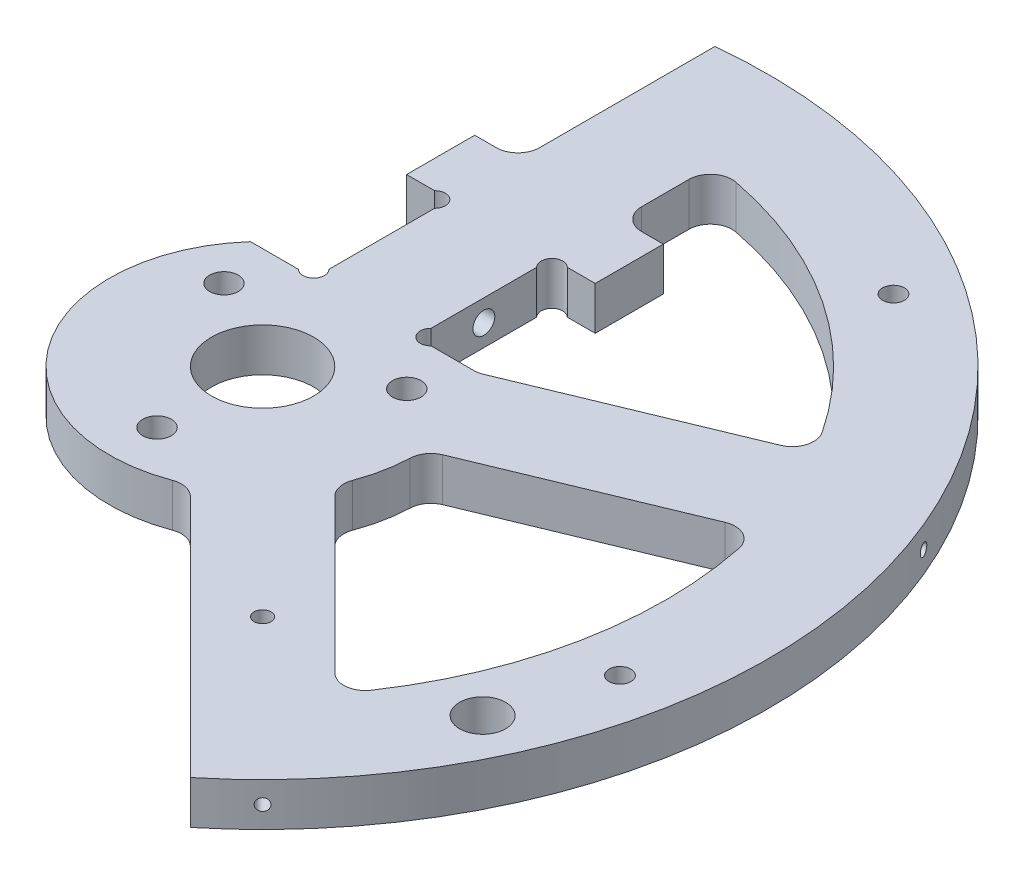
SolidWorks part; units mm, degrees
material "6061 Alloy"
ref_plane "Front Plane" through (0, 0, 0) normal (0, 0, 1) x (1, 0, 0)
ref_plane "Top Plane" through (0, 0, 0) normal (0, 1, 0) x (1, 0, 0)
ref_plane "Right Plane" through (0, 0, 0) normal (1, 0, 0) x (0, 0, -1)
sketch "Sketch1" plane through (0, 0, 0) normal (0, 1, 0) x (1, 0, 0)
  line L0 (0, 0) -> (0, 74.3) construction
  line L1 (0, 0) -> (52.538, -52.538) construction
  line L2 (20.3033, -9.6967) -> (46.898, -36.2914)
  line L3 (7.5, 15) -> (7.5, 35)
  line L4 (-7.5, -3.1066) -> (-5.3033, -5.3033) construction
  line L5 (-7.5, 21.2132) -> (-7.5, 14.1697) construction
  line L6 (-7.5, -3.1066) -> (-7.5, 74.3) construction
  line L7 (7.5, 3.1066) -> (7.5, 74.3) construction
  line L8 (-7.5, -3.1066) -> (47.2347, -57.8413) construction
  line L9 (7.5, 3.1066) -> (57.8413, -47.2347) construction
  line L10 (46.898, -36.2914) -> (57.573, -46.9664) construction
  line L11 (7.5, 58.8238) -> (7.5, 73.9205) construction
  line L12 (0, 0) -> (68.6442, 28.4334) construction
  line L13 (22.4686, 1.1888) -> (57.2162, 15.5818)
  line L14 (-2.8701, 6.9291) -> (0, 8.1179) construction
  line L15 (2.8701, -6.9291) -> (5.7403, -5.7403) construction
  line L16 (2.8701, -6.9291) -> (71.5144, 21.5043) construction
  line L17 (5.7403, -5.7403) -> (13.2403, -2.6336) construction
  line L18 (7.5, 3.1066) -> (13.2403, -2.6336) construction
  line L19 (7.5, 3.1066) -> (7.5, 11.2245) construction
  line L20 (0, 8.1179) -> (7.5, 11.2245) construction
  line L21 (7.5, 11.2245) -> (9.0849, 11.881) construction
  line L22 (-2.8701, 6.9291) -> (65.7741, 35.3625) construction
  line L23 (51.476, 29.44) -> (65.4235, 35.2172) construction
  line L24 (65.4235, 35.2172) -> (65.7741, 35.3625)
  line L25 (57.2162, 15.5818) -> (71.1638, 21.3591) construction
  line L26 (71.1638, 21.3591) -> (71.5144, 21.5043)
  line L27 (13.2403, -2.6336) -> (20.3033, -9.6967) construction
  line L28 (13.85, 5) -> (7.5, 5) construction
  line L29 (13.85, 17.7321) -> (13.85, 15) construction
  line L30 (13.85, 45) -> (7.5, 45)
  line L31 (-13.85, 17.7321) -> (-13.85, 15) construction
  line L32 (13.85, 5) -> (-13.85, 45) construction
  line L33 (13.85, 45) -> (-13.85, 5) construction
  line L34 (-13.85, 35) -> (-7.5, 35)
  line L35 (-13.85, 35) -> (-13.85, 15) construction
  line L36 (-16.7705, 15) -> (-7.5, 15)
  line L37 (-7.5, 35) -> (-7.5, 15)
  line L38 (7.5, 15) -> (16.6148, 15)
  line L39 (7.5, 15) -> (7.5, 35)
  line L40 (7.5, 35) -> (13.85, 35)
  line L41 (13.85, 15) -> (13.85, 35) construction
  line L42 (13.2403, -2.6336) -> (22.4686, 1.1888) construction
  line L43 (7.5, 5) -> (-7.5274, 5) construction
  line L44 (-7.5, 5) -> (-13.85, 5) construction
  line L45 (-7.5274, 5) -> (0, 5) construction
  line L46 (0, 5) -> (-7.5, 5) construction
  line L47 (13.85, 5) -> (13.85, 13.8548) construction
  line L48 (16.6148, 15) -> (16.7283, 15.047)
  line L49 (16.7283, 15.047) -> (51.476, 29.44)
  line L50 (13.85, 13.8548) -> (13.85, 17.7321) construction
  line L51 (9.0849, 11.881) -> (13.85, 13.8548) construction
  line L52 (7.5, 11.2245) -> (7.5, 21.2132) construction
  line L53 (7.5, 21.2132) -> (7.5, 14.1697) construction
  line L54 (-5.3033, -5.3033) -> (9.6967, -20.3033) construction
  line L55 (9.6967, -20.3033) -> (46.9664, -57.573)
  line L56 (-7.5, -3.1066) -> (-7.5, 0) construction
  line L57 (-7.5, 0) -> (-7.5, 5) construction
  line L58 (-13.85, 5) -> (-13.85, 17.7321) construction
  line L59 (-7.5, 5) -> (-7.5, 21.2132) construction
  line L60 (-7.5, 14.1697) -> (-7.5, 15) construction
  line L61 (-7.5, 15) -> (-7.5, 35) construction
  line L62 (-13.85, 15) -> (-13.85, 35) construction
  line L63 (-13.85, 35) -> (-13.85, 45)
  line L64 (13.85, 15) -> (13.85, 35) construction
  line L65 (13.85, 35) -> (13.85, 45)
  line L66 (0, 45) -> (-7.5, 45) construction
  line L67 (-7.5, 45) -> (-13.85, 45)
  line L68 (7.5, 45) -> (0, 45) construction
  line L69 (7.5, 14.1697) -> (7.5, 15) construction
  line L70 (7.5, 35.8303) -> (7.5, 45) construction
  line L71 (7.5, 45) -> (7.5, 58.8238)
  line L72 (7.5, 35) -> (7.5, 35.8303) construction
  line L73 (-7.5, 35) -> (-7.5, 35.8303) construction
  line L74 (-7.5, 45) -> (-7.5, 73.9205)
  line L75 (-7.5, 35.8303) -> (-7.5, 45) construction
  line L77 (13.85, 13.8548) -> (16.6148, 15) construction
  arc A0 (46.9664, -57.573) -> (-7.5, 73.9205) centre (0, 0) ccw
  arc A1 (46.898, -36.2914) -> (57.2162, 15.5818) centre (0, 0) ccw
  arc A2 (-7.5, 73.9205) -> (46.9664, -57.573) centre (0, 0) ccw construction
  circle A3 centre (0, 0) radius 74.3 construction
  arc A4 (41.9314, -41.9314) -> (46.898, -36.2914) centre (0, 0) ccw construction
  circle A5 centre (0, 0) radius 59.3 construction
  arc A6 (36.2914, -46.898) -> (41.9314, -41.9314) centre (0, 0) ccw construction
  arc A7 (-7.5, 58.8238) -> (36.2914, -46.898) centre (0, 0) ccw construction
  arc A8 (7.5, 58.8238) -> (0, 59.3) centre (0, 0) ccw construction
  arc A9 (0, 59.3) -> (-7.5, 58.8238) centre (0, 0) ccw construction
  arc A10 (57.2162, 15.5818) -> (54.7861, 22.6931) centre (0, 0) ccw construction
  arc A11 (51.476, 29.44) -> (7.5, 58.8238) centre (0, 0) ccw
  arc A12 (54.7861, 22.6931) -> (51.476, 29.44) centre (0, 0) ccw construction
  arc A13 (20.3033, -9.6967) -> (22.4686, 1.1888) centre (0, 0) ccw
  circle A14 centre (0, 0) radius 7.5
  arc A15 (9.6967, -20.3033) -> (15.9099, -15.9099) centre (0, 0) ccw construction
  arc A16 (15.9099, -15.9099) -> (20.3033, -9.6967) centre (0, 0) ccw construction
  arc A17 (22.4686, 1.1888) -> (20.7873, 8.6104) centre (0, 0) ccw construction
  arc A18 (16.7283, 15.047) -> (13.85, 17.7321) centre (0, 0) ccw construction
  arc A19 (20.7873, 8.6104) -> (16.7283, 15.047) centre (0, 0) ccw construction
  arc A20 (13.85, 17.7321) -> (1.7801, 22.4295) centre (0, 0) ccw construction
  arc A21 (-7.5, 21.2132) -> (-13.85, 17.7321) centre (0, 0) ccw construction
  arc A22 (1.7801, 22.4295) -> (-13.85, 17.7321) centre (0, 0) ccw construction
  arc A23 (7.5, 21.2132) -> (0, 22.5) centre (0, 0) ccw construction
  arc A24 (0, 22.5) -> (-7.5, 21.2132) centre (0, 0) ccw construction
  arc A25 (-1.7801, 22.4295) -> (-13.85, 17.7321) centre (0, 0) ccw construction
  arc A26 (-16.7705, 15) -> (9.6967, -20.3033) centre (0, 0) ccw
  arc A27 (-13.85, 17.7321) -> (-16.7705, 15) centre (0, 0) ccw construction
  arc A28 (-16.7705, 15) -> (-1.7801, 22.4295) centre (0, 0) ccw construction
  arc A29 (-13.85, 17.7321) -> (-16.7705, 15) centre (0, 0) ccw construction
  arc A30 (-13.85, 17.7321) -> (-16.7705, 15) centre (0, 0) ccw construction
  arc A31 (-16.7705, 15) -> (7.5, 21.2132) centre (0, 0) ccw construction
  point P77 (0, 25)
  dimension "D1" = 148.6
  dimension "D11" = 45
  dimension "D12" = 15
  dimension "D2" = 135
  dimension "D6" = 67.5
  dimension "D9" = 27.7
  dimension "D10" = 40
  dimension "D13" = 5
  dimension "D14" = 10
  dimension "D15" = 10
  dimension "D3" = 7.5
  dimension "D4" = 7.5
  dimension "D5" = 15
  dimension "D7" = 7.5
  dimension "D8" = 7.5
extrude "Boss-Extrude1" add sketch "Sketch1" along normal mid plane 6.35 contours L31 A26 L55 A0 L74 L67 L63 L34 L37 L36 L49 A18 L29 L38 L3 L40 L65 L30 L71 A11 L2 A13 L13 A1 A14 region at (27.267, 0, -11.9761)
hole_wizard "M5x0.8 Tapped Hole2" positions "Sketch2" profile "Sketch3" tap size "M5x0.8" standard "ANSI Metric" end condition through all
sketch "Sketch2" plane through (0, 3.175, 0) normal (0, 1, 0) x (1, 0, 0)
  line L1 (0, 0) -> (-13.4234, 7.75) construction
  line L3 (13.4234, 7.75) -> (0, 0) construction
  line L4 (0, 0) -> (0, -15.5) construction
  circle A0 centre (0, 0) radius 15.5 construction
  point P10 (-13.4234, 7.75)
  point P12 (13.4234, 7.75)
  point P16 (0, -15.5)
  dimension "D1" = 31
  dimension "D2" = 120
  dimension "D3" = 120
sketch "Sketch3" plane through (0, 3.175, 15.5) normal (1, 0, 0) x (0, 0, 1)
  line L0 (0, 0) -> (0, 6.35)
  line L1 (0, 6.35) -> (2.1, 6.35)
  line L2 (2.1, 6.35) -> (2.1, 0)
  line L5 (2.1, 0) -> (0, 0)
  line L11 (0, -6.35) -> (0, 107.95) construction
  dimension "Thru Tap Drill Dia." = 4.2
  dimension "Thru Tap Drill Depth" = 6.35
ref_plane "Plane1" through (0, 0, -74.3) normal (0, 0, -1) x (-1, 0, 0)
hole_wizard "M2.2x0.45 Tapped Hole1" positions "Sketch4" profile "Sketch5" tap size "M2.2x0.45" standard "ANSI Metric"
sketch "Sketch4" plane through (0, 0, -74.3) normal (0, 0, -1) x (-1, 0, 0)
  point P0 (0, 0)
sketch "Sketch5" plane through (0, 0, -74.3) normal (1, 0, 0) x (0, 1, 0)
  line L0 (0, 0) -> (0, 10.5258)
  line L1 (0, 10.5258) -> (0.875, 10)
  line L2 (0.875, 10) -> (0.875, 0)
  line L5 (0.875, 0) -> (0, 0)
  line L10 (0, 10.5258) -> (-0.875, 10) construction
  line L11 (0, -6.35) -> (0, 107.95) construction
  dimension "Tap Drill Dia." = 1.75
  dimension "Tap Drill Depth" = 10
  dimension "Drill Angle" = 118
pattern_circular "CirPattern1" count 3 over 135 about axis through (0, 3.175, 0) along (0, -1, 0) of "M2.2x0.45 Tapped Hole1"
hole_wizard "M3 Clearance Hole1" positions "Sketch6" profile "Sketch7" hole size "M3" standard "ANSI Metric" end condition up to next
sketch "Sketch6" plane through (-7.5, 0, 0) normal (-1, 0, 0) x (0, 0, 1)
  line L1 (-35, 3.175) -> (-15, 3.175)
  line L2 (-35, 3.175) -> (-35, -3.175)
  line L3 (-35, -3.175) -> (-15, -3.175)
  line L4 (-15, 3.175) -> (-15, -3.175)
  line L5 (-35, 3.175) -> (-15, -3.175) construction
  line L6 (-35, -3.175) -> (-15, 3.175) construction
  point P199 (-25, 0)
sketch "Sketch7" plane through (-7.5, 0, -25) normal (0, 1, 0) x (0, 0, 1)
  line L0 (0, 0) -> (0, 15)
  line L1 (0, 15) -> (1.6, 15)
  line L2 (1.6, 15) -> (1.6, 0)
  line L5 (1.6, 0) -> (0, 0)
  line L11 (0, -6.35) -> (0, 107.95) construction
  dimension "Thru Hole Dia." = 3.2
  dimension "Thru Hole Depth" = 15
hole_wizard "CSK for M3 Flat Head Machine Screw1" positions "Sketch8" profile "Sketch9" countersink size "M3" standard "ANSI Metric" end condition up to next
sketch "Sketch8" plane through (0, -3.175, 0) normal (0, -1, 0) x (-1, 0, 0)
  line L0 (-58.1606, -11.5689) -> (-72.8723, -14.4952) construction
  line L2 (-32.9453, 49.3061) -> (-41.2789, 61.7782) construction
  arc A0 (-57.2162, 15.5818) -> (-46.898, -36.2914) centre (0, 0) ccw construction
  arc A1 (7.5, 73.9205) -> (-46.9664, -57.573) centre (0, 0) ccw construction
  arc A2 (-7.5, 58.8238) -> (-51.476, 29.44) centre (0, 0) ccw construction
  point P19 (-65.5165, -13.032)
  point P21 (-37.1121, 55.5422)
sketch "Sketch9" plane through (37.1121, -3.175, -55.5422) normal (1, 0, 0) x (0, 0, -1)
  line L0 (0, 0) -> (0, 6.35)
  line L1 (0, 6.35) -> (1.6, 6.35)
  line L2 (1.6, 6.35) -> (1.6, 1.55)
  line L3 (1.6, 1.55) -> (3.15, 0)
  line L5 (3.15, 0) -> (0, 0)
  line L6 (-1.6, 1.55) -> (-3.15, 0) construction
  line L11 (0, -6.35) -> (0, 107.95) construction
  dimension "Thru Hole Dia." = 3.2
  dimension "Thru Hole Depth" = 6.35
  dimension "Near C'Sink Dia." = 6.3
  dimension "Near C'Sink Angle" = 90
hole_wizard "M3x0.5 Tapped Hole1" positions "Sketch10" profile "Sketch11" tap size "M3x0.5" standard "ANSI Metric" end condition up to next
sketch "Sketch10" plane through (0, -3.175, 0) normal (0, -1, 0) x (-1, 0, 0)
  line L5 (-9.6967, -20.3033) -> (-46.9664, -57.573) construction
  line L6 (0, 0) -> (-52.538, -52.538) construction
  arc A2 (7.5, 73.9205) -> (-46.9664, -57.573) centre (0, 0) ccw construction
  point P37 (-31.8198, -31.8198)
  point P38 (0, 0)
  dimension "D2" = 45
sketch "Sketch11" plane through (31.8198, -3.175, 31.8198) normal (1, 0, 0) x (0, 0, -1)
  line L0 (0, 0) -> (0, 6.35)
  line L1 (0, 6.35) -> (1.25, 6.35)
  line L2 (1.25, 6.35) -> (1.25, 0)
  line L5 (1.25, 0) -> (0, 0)
  line L11 (0, -6.35) -> (0, 107.95) construction
  dimension "Thru Tap Drill Dia." = 2.5
  dimension "Thru Tap Drill Depth" = 6.35
cosmetic thread "Hole Thread2" parameters "D2"=3
sketch "Sketch12" plane through (0, 3.175, 0) normal (0, 1, 0) x (1, 0, 0)
  line L0 (-13.85, 35) -> (-7.5, 35) construction
  line L1 (-7.5, 35) -> (-7.5, 33.8775)
  line L2 (-7.5, 15) -> (-8.6225, 15)
  line L3 (-7.5, 15) -> (-7.5, 16.1225)
  line L4 (-7.5, 16.1225) -> (-8.6225, 16.1225)
  line L5 (-8.6225, 15) -> (-8.6225, 16.1225)
  line L6 (-7.5, 15) -> (-8.6225, 16.1225) construction
  line L7 (-7.5, 16.1225) -> (-8.6225, 15) construction
  line L8 (-7.5, 35) -> (-8.6225, 35)
  line L9 (-8.6225, 35) -> (-8.6225, 33.8775)
  line L10 (-7.5, 33.8775) -> (-8.6225, 33.8775)
  line L11 (-7.5, 35) -> (-8.6225, 33.8775) construction
  line L12 (-8.6225, 35) -> (-7.5, 33.8775) construction
  line L14 (7.5, 35) -> (8.6225, 35)
  line L15 (7.5, 35) -> (7.5, 33.8775)
  line L16 (7.5, 33.8775) -> (8.6225, 33.8775)
  line L17 (8.6225, 35) -> (8.6225, 33.8775)
  line L18 (7.5, 35) -> (8.6225, 33.8775) construction
  line L19 (7.5, 33.8775) -> (8.6225, 35) construction
  line L20 (7.5, 15) -> (8.6225, 15)
  line L21 (7.5, 15) -> (7.5, 16.1225)
  line L22 (7.5, 16.1225) -> (8.6225, 16.1225)
  line L23 (8.6225, 15) -> (8.6225, 16.1225)
  line L24 (7.5, 15) -> (8.6225, 16.1225) construction
  line L25 (7.5, 16.1225) -> (8.6225, 15) construction
  circle A0 centre (-8.6225, 16.1225) radius 1.5875
  circle A1 centre (-8.6225, 33.8775) radius 1.5875
  circle A2 centre (8.6225, 33.8775) radius 1.5875
  circle A3 centre (8.6225, 16.1225) radius 1.5875
  point P8 (-8.0613, 15.5613)
  point P12 (-8.0613, 34.4387)
  point P21 (8.0613, 34.4387)
  point P26 (8.0613, 15.5613)
  line M33 (16.6148, 15) -> (7.5, 15)
  line M34 (7.5, 15) -> (7.5, 35)
  line M35 (7.5, 35) -> (13.85, 35)
  line M40 (-7.5, 15) -> (-16.7705, 15)
  line M47 (-13.85, 35) -> (-7.5, 35)
  line M48 (-7.5, 35) -> (-7.5, 15)
  dimension "D1" = 3.175
extrude "Cut-Extrude1" cut sketch "Sketch12" against normal up to next contours A0 M48 | A0 M40 | A3 M33 | A3 M34 | A2 M34 | A2 M35 | A1 M48 | A1 M47 region at (-7.3115, 3.175, -33.8775) region at (-7.3115, 3.175, -16.1225) region at (-8.6225, 3.175, -35.1885) region at (-8.6225, 3.175, -14.8115) region at (8.6225, 3.175, -35.1885) region at (7.3115, 3.175, -16.1225) region at (7.3115, 3.175, -33.8775) region at (8.6225, 3.175, -14.8115)
fillet "Fillet1" radius 3.175 10 edges at (9.6967, 0, 20.3033) (22.4686, 0, -1.1888) (57.2162, 0, -15.5818) (46.898, 0, 36.2914) (20.3033, 0, 9.6967) (51.476, 0, -29.44) (16.6148, 0, -15) (7.5, 0, -45) (7.5, 0, -58.8238) (-7.5, 0, -45)
hole_wizard "1/4 Clearance Hole1" positions "Sketch13" profile "Sketch14" hole size "1/4" standard "ANSI Inch" end condition up to next
sketch "Sketch13" plane through (0, 3.175, 0) normal (0, 1, 0) x (1, 0, 0)
  line L1 (53.7441, -25.0613) -> (67.3387, -31.4005) construction
  line L2 (11.2081, -21.8147) -> (46.9664, -57.573) construction
  arc A2 (46.9664, -57.573) -> (-7.5, 73.9205) centre (0, 0) ccw construction
  arc A3 (49.1414, -33.1906) -> (58.1022, 11.8585) centre (0, 0) ccw construction
  point P85 (60.5414, -28.2309)
  dimension "D1" = 20
sketch "Sketch14" plane through (60.5414, 3.175, 28.2309) normal (1, 0, 0) x (0, 0, 1)
  line L0 (0, 0) -> (0, 6.35)
  line L1 (0, 6.35) -> (3.3782, 6.35)
  line L2 (3.3782, 6.35) -> (3.3782, 0)
  line L5 (3.3782, 0) -> (0, 0)
  line L11 (0, -6.35) -> (0, 107.95) construction
  dimension "Thru Hole Dia." = 6.7564
  dimension "Thru Hole Depth" = 6.35
